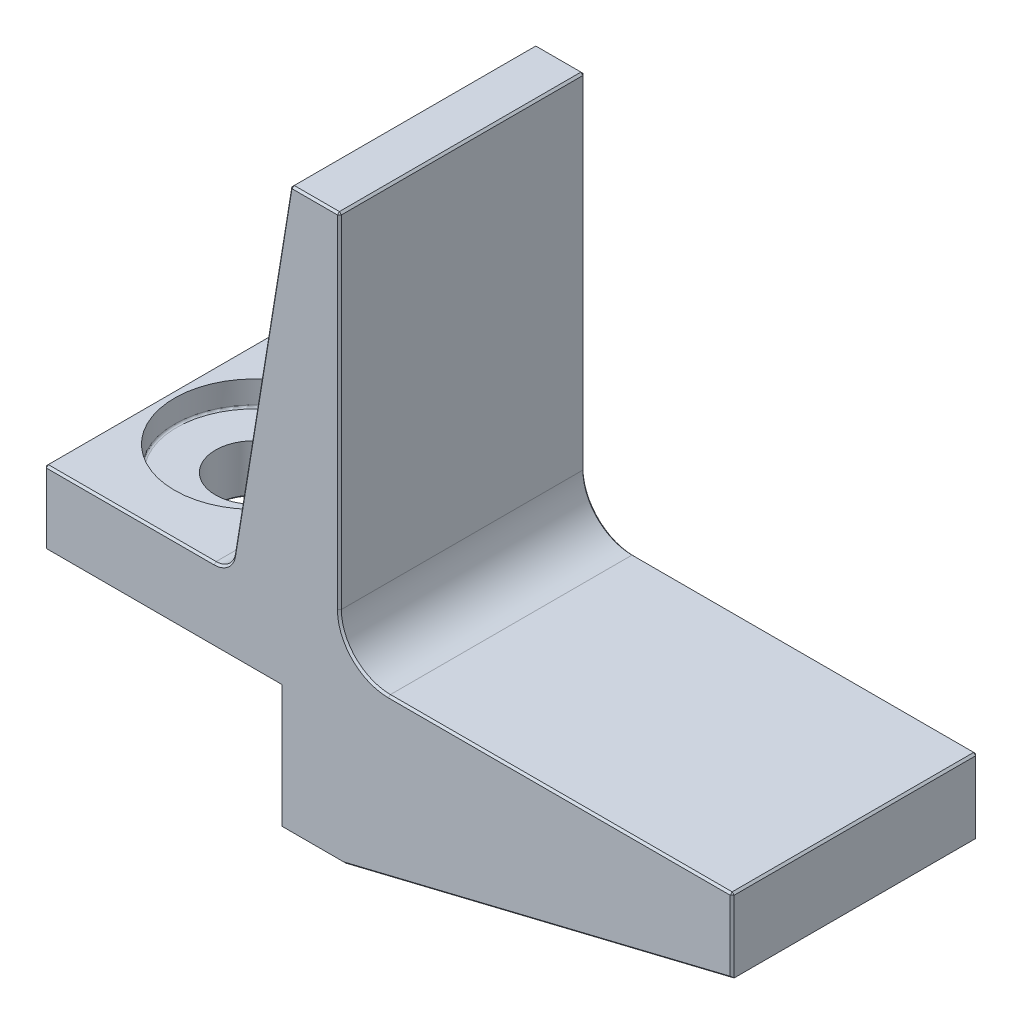
SolidWorks part; units mm, degrees
material "7075-T6 (SN)"
ref_plane "Front Plane" through (0, 0, 0) normal (0, 0, 1) x (1, 0, 0)
ref_plane "Top Plane" through (0, 0, 0) normal (0, 1, 0) x (1, 0, 0)
ref_plane "Right Plane" through (0, 0, 0) normal (1, 0, 0) x (0, 0, -1)
sketch "Sketch1" plane through (0, 0, 0) normal (0, 0, 1) x (1, 0, 0)
  line L0 (0, 0) -> (50.8, 0)
  line L1 (50.8, 0) -> (50.8, -9.525)
  line L2 (-7.6808, -5.8961) -> (-38.1608, -5.8961)
  line L3 (-38.1608, -5.8961) -> (-38.1608, 3.6289)
  line L4 (-38.1608, 3.6289) -> (-14.0308, 3.6289)
  line L5 (-14.0308, 3.6289) -> (-6.35, 50.8)
  line L6 (-6.35, 50.8) -> (0, 50.8)
  line L7 (0, 50.8) -> (0, 0)
  line L8 (-7.6808, -5.8961) -> (-7.6808, -21.7711)
  line L9 (-7.6808, -21.7711) -> (0.5742, -21.7711)
  line L10 (0.5742, -21.7711) -> (50.8, -9.525)
  dimension "D1" = 50.8
  dimension "D2" = 50.8
  dimension "D3" = 9.525
  dimension "D4" = 38.1608
  dimension "D5" = 6.35
  dimension "D6" = 24.13
  dimension "D7" = 30.48
  dimension "D8" = 9.525
  dimension "D9" = 15.875
  dimension "D10" = 8.255
  dimension "D11" = 3.6289
extrude "Boss-Extrude1" add sketch "Sketch1" along normal blind 31.75
hole_wizard "CBORE for 3/8 Binding Head Machine Screw1" positions "Sketch6" profile "Sketch3" counterbore size "3/8" standard "ANSI Inch" end condition through all
sketch "Sketch6" plane through (0, 3.6289, 0) normal (0, 1, 0) x (1, 0, 0)
  line L1 (-38.1608, -31.75) -> (-38.1608, 0) construction
  point P0 (-26.8578, -15.875)
  point P8 (-38.1608, -15.875)
  dimension "D1" = 11.303
sketch "Sketch3" plane through (-26.8578, 3.6289, 15.875) normal (1, 0, 0) x (0, 0, 1)
  line L0 (0, 0) -> (0, 25.4)
  line L1 (0, 25.4) -> (5.0419, 25.4)
  line L3 (5.0419, 25.4) -> (5.0419, 3.175)
  line L4 (10.3378, 3.175) -> (5.0419, 3.175)
  line L5 (10.3378, 3.175) -> (10.3378, 0)
  line L7 (10.3378, 0) -> (0, 0)
  line L11 (0, 0) -> (0, 107.95) construction
  dimension "Thru Hole Dia." = 10.0838
  dimension "Thru Hole Depth" = 25.4
  dimension "C'Bore Depth" = 3.175
fillet "Fillet1" radius 2.54 1 edges at (-14.0308, 3.6289, 15.875)
fillet "Fillet2" radius 6.35 1 edges at (0, 0, 15.875)
chamfer "Chamfer1" distance 0.254 angle 45 31 edges at (-6.35, 50.8, 15.875) (-3.175, 50.8, 0) (-10.0168, 28.2803, 0) (-14.5453, 4.2339, 0) (-27.1757, 3.6289, 0) (-38.1608, -1.1336, 0) (-22.9208, -5.8961, 0) (50.8, -4.7625, 0) (28.575, 0, 0) (1.8599, 1.8599, 0) (0, 28.575, 0) (50.8, -4.7625, 31.75) (-22.9208, -5.8961, 31.75) (-38.1608, -5.8961, 15.875) (-38.1608, -1.1336, 31.75) (-38.1608, 3.6289, 15.875) (-27.1757, 3.6289, 31.75) (-14.5453, 4.2339, 31.75) (-10.0168, 28.2803, 31.75) (-3.175, 50.8, 31.75) (0, 50.8, 15.875) (0, 28.575, 31.75) (1.8599, 1.8599, 31.75) (28.575, 0, 31.75) (50.8, 0, 15.875) (-7.6808, -13.8336, 0) (-3.5533, -21.7711, 0) (25.6871, -15.6481, 0) (25.6871, -15.6481, 31.75) (-3.5533, -21.7711, 31.75) (-7.6808, -13.8336, 31.75) first distance on face at (-3.175, 50.8, 15.875) first distance on face at (-10.0168, 28.2803, 15.875) first distance on face at (-14.7412, 4.4643, 15.875) first distance on face at (-26.8578, 3.6289, 26.2128) first distance on face at (-38.1608, -1.1336, 15.875) first distance on face at (-31.8997, -5.8961, 15.875) first distance on face at (50.8, -4.7625, 15.875) first distance on face at (-1.562, 4.1795, 0) first distance on face at (2.5174, 2.5174, 15.875) first distance on face at (0, 28.575, 15.875) first distance on face at (-1.562, 4.1795, 31.75) first distance on face at (-7.6808, -13.8336, 15.875) first distance on face at (-3.5533, -21.7711, 15.875) first distance on face at (25.6871, -15.6481, 15.875)
fillet "Fillet3" radius 0.254 1 edges at (-26.8578, 0.4539, 26.2128)
chamfer "Chamfer2" distance 0.254 angle 45 1 edges at (-31.8997, -5.8961, 15.875)
